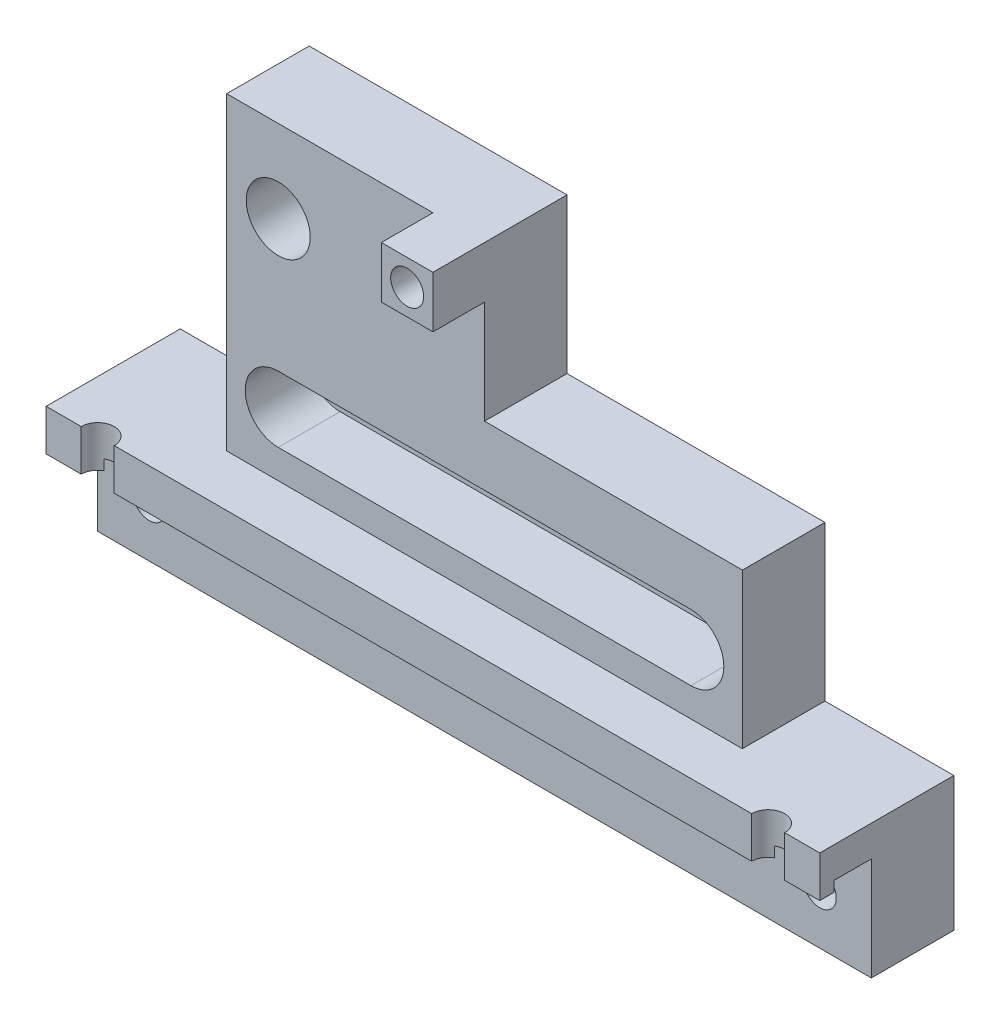
SolidWorks part; units mm, degrees
ref_plane "Front Plane" through (0, 0, 0) normal (0, 0, 1) x (1, 0, 0)
ref_plane "Top Plane" through (0, 0, 0) normal (0, 1, 0) x (1, 0, 0)
ref_plane "Right Plane" through (0, 0, 0) normal (1, 0, 0) x (0, 0, -1)
sketch "Esquisse1" plane through (0, 0, 0) normal (0, 0, 1) x (1, 0, 0)
  line L0 (0, 15) -> (0, 0)
  line L1 (-25, 15) -> (0, 15)
  line L2 (-25, 15) -> (-25, -15)
  line L3 (-25, -15) -> (25, -15)
  line L4 (0, 0) -> (25, 0)
  line L5 (25, 0) -> (25, -15)
  line L6 (0, -55) -> (0, 55) construction
  point P4 (-25, 0)
  point P6 (0, -15)
  point P7 (0, 0)
  dimension "D1" = 15
  dimension "D2" = 50
  dimension "D3" = 30
extrude "Main Extrusion" add sketch "Esquisse1" along normal blind 8
sketch "Esquisse2" plane through (0, 0, 8) normal (0, 0, 1) x (1, 0, 0)
  line L0 (-20, -12.2) -> (20, -12.2)
  line L1 (20, -5.8) -> (-20, -5.8)
  line L2 (0, -55) -> (0, 55) construction
  line L4 (-25, -15) -> (25, -15) construction
  arc A0 (20, -12.2) -> (20, -5.8) centre (20, -9) ccw
  arc A3 (-20, -5.8) -> (-20, -12.2) centre (-20, -9) ccw
  point P5 (0, -5.8)
  dimension "D3" = 6
  dimension "D1" = 40
  dimension "D2" = 3.2
extrude "Double Circle" cut sketch "Esquisse2" against normal blind 6
sketch "Esquisse3" plane through (0, 0, 8) normal (0, 0, 1) x (1, 0, 0)
  line L1 (0, 15) -> (-25, 15) construction
  line L2 (0, -4.4) -> (0, 4.4) construction
  line L10 (0, 15) -> (-5, 15)
  line L11 (0, 15) -> (0, 10)
  line L12 (0, 10) -> (-5, 10)
  line L13 (-5, 15) -> (-5, 10)
  point P0 (-4.2434, 10)
  dimension "D1" = 5
extrude "Fixing Support" add sketch "Esquisse3" along normal blind 5
sketch "Esquisse4" plane through (0, 0, 13) normal (0, 0, 1) x (1, 0, 0)
  line L4 (0, 10) -> (0, 15) construction
  line L6 (0, 15) -> (-5, 15) construction
  circle A1 centre (-2.5, 12.5) radius 1.6
  point P0 (0, 0)
  point P2 (0, 0)
  dimension "D2" = 3.2
  dimension "D1" = 2.5
  dimension "D4" = 2.5
extrude "Fixing Hole" cut sketch "Esquisse4" against normal through all
sketch "Esquisse5" plane through (0, 0, 8) normal (0, 0, 1) x (1, 0, 0)
  line L1 (-25, -15) -> (25, -15) construction
  line L3 (-25, 15) -> (-25, -15) construction
  circle A0 centre (-20, 7) radius 3.1
  point P2 (0, 11.0821)
  point P5 (-17.6632, 10)
  dimension "D1" = 6.2
  dimension "D2" = 22
  dimension "D3" = 5
extrude "Gear Linear Holes" cut sketch "Esquisse5" against normal through all
ref_plane "Plan1" through (15, 0, 0) normal (1, 0, 0) x (0, 0, -1)
ref_axis "Axe1" through (15, 0, -0.535) along (0, 0, 1)
sketch "Esquisse8" plane through (0, 0, 0) normal (1, 0, 0) x (0, 0, -1)
  line L0 (-8, -18) -> (-8, -28)
  line L1 (-8, -18) -> (-11.6, -18)
  line L2 (-11.6, -18) -> (-11.6, -19)
  line L3 (-11.6, -19) -> (-13, -19)
  line L4 (-13, -19) -> (-13, -15)
  line L5 (-13, -15) -> (0, -15)
  line L6 (-8, -28) -> (0, -28)
  line L7 (0, -28) -> (0, -15)
  line L8 (-13, 10) -> (-13, 15) construction
  line L10 (0, -15) -> (0, 0) construction
  line L11 (-8, -15) -> (0, -15) construction
  line L12 (-8, -15) -> (-8, 0) construction
  point P14 (0, -15)
  point P17 (-13, -15.9424)
  dimension "D1" = 1.4
  dimension "D3" = 1
  dimension "D4" = 3
  dimension "D5" = 10
extrude "Boss.-Extru.1" add sketch "Esquisse8" along normal mid plane 75
sketch "Esquisse9" plane through (0, -15, 0) normal (0, 1, 0) x (1, 0, 0)
  line L1 (-37.5, 0) -> (-37.5, -13) construction
  line L2 (37.5, -13) -> (-37.5, -13) construction
  line L3 (37.5, -13) -> (-37.5, -13) construction
  line L4 (37.5, 0) -> (37.5, -13) construction
  circle A0 centre (-32.5, -13) radius 1.6
  circle A1 centre (32.5, -13) radius 1.6
  dimension "D1" = 3.2
  dimension "D3" = 3.2
  dimension "D2" = 5
  dimension "D4" = 5
extrude "Enlèv. mat.-Extru.2" cut sketch "Esquisse9" against normal through all
sketch "Esquisse10" plane through (0, 0, 0) normal (0, 0, -1) x (-1, 0, 0)
  line L0 (37.5, -28) -> (37.5, -15) construction
  line L1 (-37.5, -28) -> (-37.5, -15) construction
  line L2 (-37.5, -28) -> (37.5, -28) construction
  circle A0 centre (-32.5, -23) radius 1.6
  circle A1 centre (32.5, -23) radius 1.6
  dimension "D2" = 3.2
  dimension "D1" = 5
  dimension "D3" = 5
  dimension "D4" = 5
extrude "Enlèv. mat.-Extru.3" cut sketch "Esquisse10" against normal up to surface (8 mm away) up to face at (0, -23, 8)
mirror "Symétrie4" [suppressed] of bodies 113 111
sketch "Esquisse7" [suppressed] plane through (-37.5, 0, 0) normal (-1, 0, 0) x (0, 0, 1)
  line L1 (10.7, 45) -> (-29.3, 45)
  line L2 (10.7, 45) -> (10.7, -55)
  line L3 (10.7, -55) -> (-29.3, -55)
  line L4 (-29.3, 45) -> (-29.3, -55)
  line L5 (10.7, 25) -> (10.7, 20) construction
  line L6 (10.7, 25) -> (0, 25) construction
  dimension "D1" = 20
  dimension "D2" = 100
  dimension "D3" = 40
extrude "Enlèv. mat.-Extru.1" [suppressed] cut sketch "Esquisse7" against normal through all both and the other way through all
